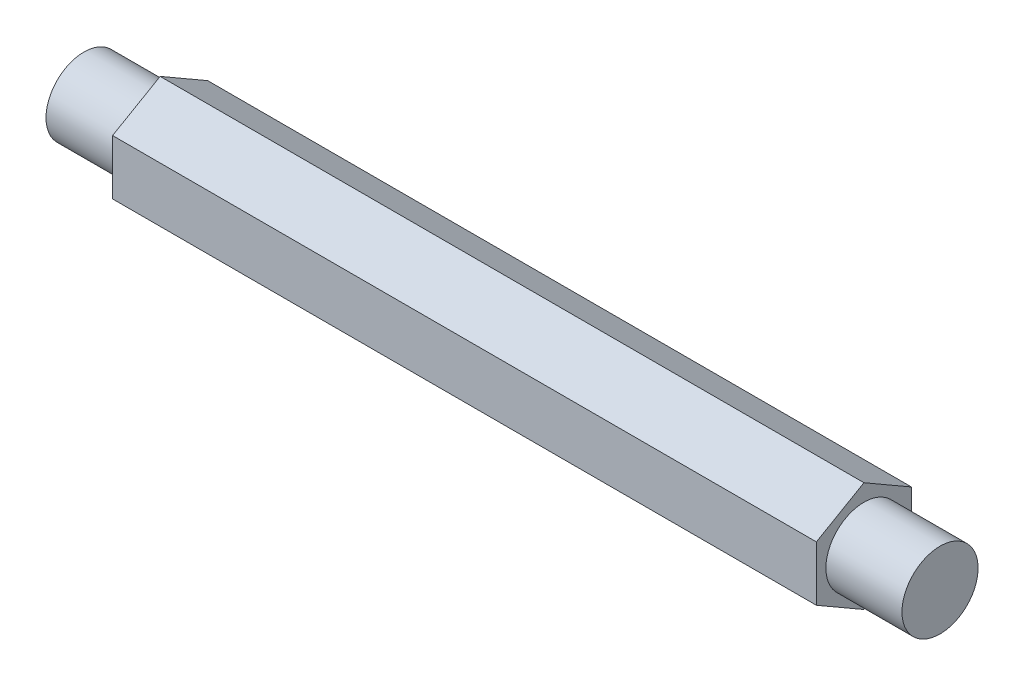
SolidWorks part; units mm, degrees
material "Chrome Stainless Steel"
ref_plane "Front Plane" through (0, 0, 0) normal (0, 0, 1) x (1, 0, 0)
ref_plane "Top Plane" through (0, 0, 0) normal (0, 1, 0) x (1, 0, 0)
ref_plane "Right Plane" through (0, 0, 0) normal (1, 0, 0) x (0, 0, -1)
sketch "Sketch1" plane through (0, 0, 0) normal (0, 0, 1) x (1, 0, 0)
  line L0 (0, 2) -> (-4, 2)
  line L1 (-4, 2) -> (-4, 0)
  line L2 (-6.1852, 0) -> (29.7037, 0) construction
  line L3 (41, 0) -> (41, 2)
  line L4 (41, 2) -> (37, 2)
  line L5 (37, 2) -> (37, 2.5)
  line L6 (37, 2.5) -> (0, 2.5)
  line L7 (0, 2.5) -> (0, 2)
  line L8 (-4, 0) -> (41, 0)
  line L9 (37, 10.2725) -> (37, 5.3725) construction
  dimension "D1" = 5
  dimension "D2" = 4
  dimension "D3" = 4
  dimension "D4" = 4
  dimension "D5" = 4
revolve "Revolve1" add sketch "Sketch1" angle 360 about L2
sketch "Sketch2" plane through (0, 0, 0) normal (1, 0, 0) x (0, 0, -1)
  line L1 (0, 2.8868) -> (-2.5, 1.4434)
  line L2 (-2.5, 1.4434) -> (-2.5, -1.4434)
  line L3 (-2.5, -1.4434) -> (0, -2.8868)
  line L4 (0, -2.8868) -> (2.5, -1.4434)
  line L5 (2.5, -1.4434) -> (2.5, 1.4434)
  line L6 (2.5, 1.4434) -> (0, 2.8868)
  circle A0 centre (0, 0) radius 2.5 construction
extrude "Boss-Extrude1" add sketch "Sketch2" along normal up to surface (37 mm away) up to face at (37, 0, 2.5)
ref_axis "Axis1" through (18.4956, 0, 0) along (-1, 0, 0)
